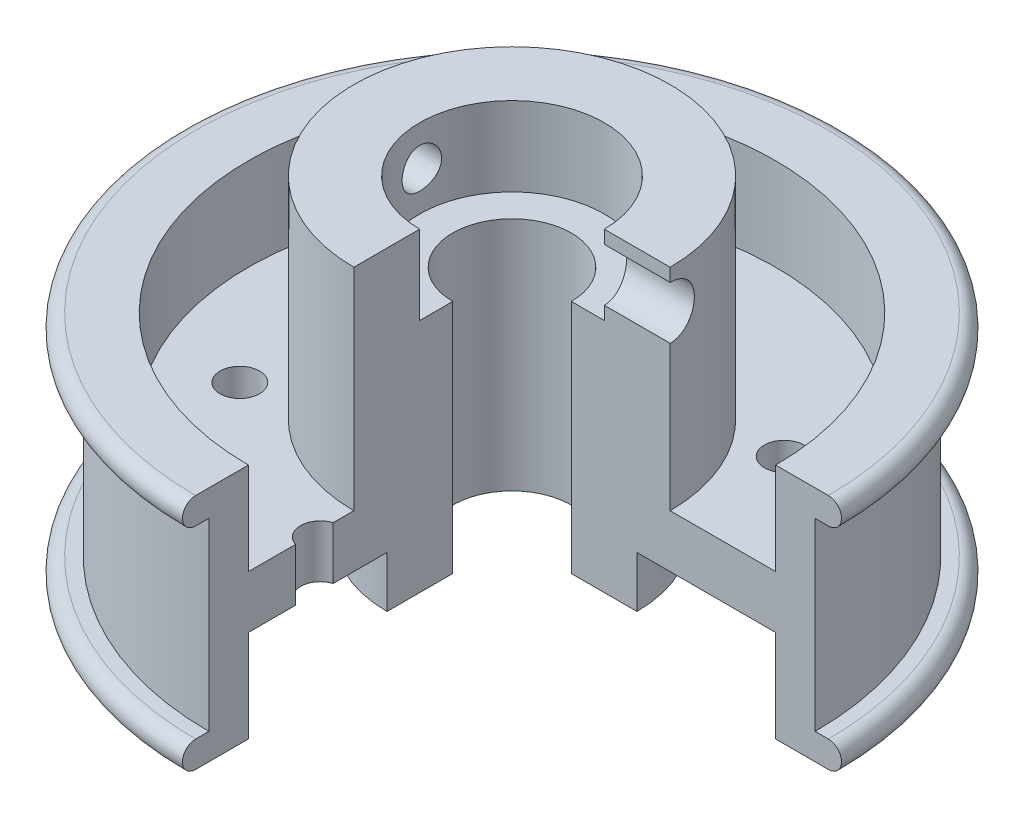
SolidWorks part; units mm, degrees
ref_plane "Front Plane" through (0, 0, 0) normal (0, 0, 1) x (1, 0, 0)
ref_plane "Top Plane" through (0, 0, 0) normal (0, 1, 0) x (1, 0, 0)
ref_plane "Right Plane" through (0, 0, 0) normal (1, 0, 0) x (0, 0, -1)
sketch "Sketch1" plane through (0, 0, 0) normal (0, 0, 1) x (1, 0, 0)
  line L0 (0, 0) -> (-31.75, 0)
  line L1 (-31.75, 0) -> (-31.75, -101.6)
  line L2 (-31.75, -101.6) -> (-82.55, -101.6)
  line L3 (-82.55, -101.6) -> (-82.55, -57.15)
  line L4 (-82.55, -57.15) -> (-114.3, -57.15)
  line L5 (-114.3, -57.15) -> (-114.3, -69.85)
  line L6 (-114.3, -69.85) -> (-101.6, -69.85)
  line L7 (-101.6, -69.85) -> (-101.6, -158.75)
  line L8 (-101.6, -158.75) -> (-114.3, -158.75)
  line L9 (-114.3, -158.75) -> (-114.3, -171.45)
  line L10 (-114.3, -171.45) -> (-82.55, -171.45)
  line L11 (-82.55, -171.45) -> (-82.55, -127)
  line L12 (-82.55, -127) -> (-15.748, -127)
  line L13 (-15.748, -127) -> (-15.748, -151.638)
  line L14 (-15.748, -151.638) -> (15.875, -151.638)
  line L15 (15.875, -151.638) -> (15.875, -38.1)
  line L16 (15.875, -38.1) -> (0, -38.1)
  line L17 (0, -38.1) -> (0, 0)
  line L18 (44.45, 0) -> (44.45, -157.7553) construction
  point P21 (-114.3, -63.5)
  dimension "D1" = 152.4
  dimension "D2" = 254
  dimension "D3" = 88.9
  dimension "D4" = 57.15
  dimension "D5" = 317.5
  dimension "D6" = 66.802
  dimension "D7" = 19.05
  dimension "D8" = 44.45
  dimension "D9" = 19.812
  dimension "D10" = 69.85
  dimension "D11" = 101.6
  dimension "D12" = 114.3
  dimension "D13" = 12.7
  dimension "D14" = 171.45
  dimension "D15" = 38.1
revolve "Revolve1" add sketch "Sketch1" angle 360 about L18
fillet "Fillet2" 2 edges at (-114.3, -171.45, 0) (-114.3, -158.75, 0) type full round first side face at (-82.55, -171.45, 0) second side face at (-114.3, -158.75, 0) middle face at (-114.3, -171.45, 0)
fillet "Fillet3" 2 edges at (-114.3, -69.85, 0) (-114.3, -57.15, 0) type full round first side face at (-101.6, -69.85, 0) second side face at (-114.3, -57.15, 0) middle face at (-114.3, -69.85, 0)
sketch "Sketch2" plane through (0, -101.6, 0) normal (0, 1, 0) x (1, 0, 0)
  arc A0 (120.0381, 57.9568) -> (51.0693, 95.0197) centre (44.45, 0) ccw
  circle A1 centre (41.5461, 95.2057) radius 9.525
  circle A2 centre (125.4486, 50.1177) radius 9.525
  circle A3 centre (128.3525, -45.088) radius 9.525
  circle A4 centre (47.3539, -95.2057) radius 9.525
  circle A5 centre (-36.5486, -50.1177) radius 9.525
  circle A6 centre (-39.4525, 45.088) radius 9.525
  arc A7 (132.4362, -36.4828) -> (130.0491, 41.7774) centre (44.45, 0) ccw
  arc A8 (56.848, -94.4397) -> (123.4298, -53.2423) centre (44.45, 0) ccw
  arc A9 (-31.1381, -57.9568) -> (37.8307, -95.0197) centre (44.45, 0) ccw
  arc A10 (-43.5362, 36.4828) -> (-41.1491, -41.7774) centre (44.45, 0) ccw
  arc A11 (32.052, 94.4397) -> (-34.5298, 53.2423) centre (44.45, 0) ccw
  point P18 (44.45, 0)
  point P27 (0, 0)
  dimension "D1" = 190.5
  dimension "D2" = 19.05
  dimension "D3" = 6
extrude "Cut-Extrude1" cut sketch "Sketch2" against normal through all and the other way through all contours A5 | A6 | A4 | A2 | A3 A1 | A1 region at (125.4486, -101.6, -50.1177) region at (128.3525, -101.6, 45.088) region at (-39.4525, -101.6, -45.088) region at (47.3539, -101.6, 95.2057) region at (-36.5486, -101.6, 50.1177)
ref_plane "Plane1" through (44.45, 0, 0) normal (1, 0, 0) x (0, 0, -1)
sketch "Sketch6" plane through (44.45, 0, 0) normal (1, 0, 0) x (0, 0, -1)
  line L0 (-152.4, -171.45) -> (152.4, -171.45) construction
  line L1 (-152.4, -171.45) -> (152.4, -171.45) construction
  circle A0 centre (0, -19.05) radius 12.7
  circle A1 centre (0, -19.05) radius 9.525
  arc A2 (152.4, -171.45) -> (152.4, -158.75) centre (152.4, -165.1) ccw construction
  point P11 (0, -171.45)
  dimension "D1" = 19.05
  dimension "D2" = 25.4
  dimension "D3" = 152.4
extrude "Cut-Extrude12" cut sketch "Sketch6" against normal through all both and the other way through all contours A1
extrude "Cut-Extrude13" cut sketch "Sketch6<3>" along normal blind 256.54
sketch "Sketch6<3>" plane through (44.45, 0, 0) normal (1, 0, 0) x (0, 0, -1) same geometry as "Sketch6"
sketch "Sketch5" plane through (0, -38.1, 0) normal (0, 1, 0) x (1, 0, 0)
  line L1 (44.45, 0) -> (274.9035, 0)
  line L2 (44.45, 0) -> (44.45, -214.1516)
  line L3 (44.45, -214.1516) -> (274.9035, -214.1516)
  line L4 (274.9035, 0) -> (274.9035, -214.1516)
extrude "Cut-Extrude10" cut sketch "Sketch5" against normal through all both and the other way through all
